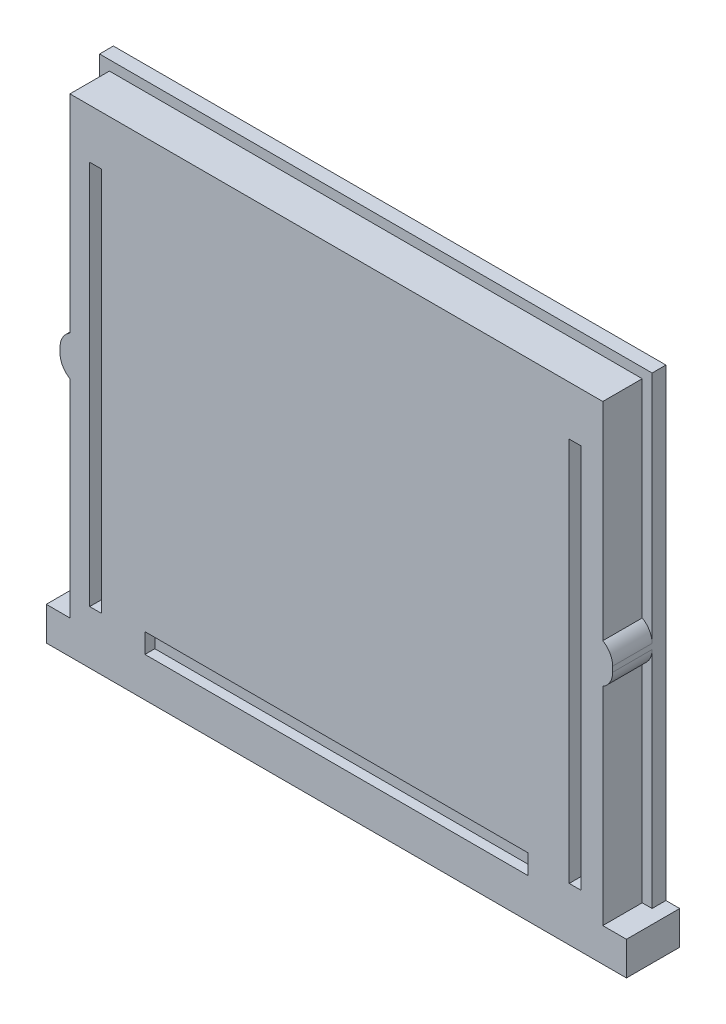
SolidWorks part; units mm, degrees
ref_plane "Спереди" through (0, 0, 0) normal (0, 0, 1) x (1, 0, 0)
ref_plane "Сверху" through (0, 0, 0) normal (0, 1, 0) x (1, 0, 0)
ref_plane "Справа" through (0, 0, 0) normal (1, 0, 0) x (0, 0, -1)
sketch "Skizze1" plane through (0, 0, 0) normal (0, 0, 1) x (1, 0, 0)
  line L1 (33.3661, 23) -> (5.3661, 23)
  line L2 (33.3661, 23) -> (33.3661, 0)
  line L3 (33.3661, 0) -> (5.3661, 0)
  line L4 (5.3661, 23) -> (5.3661, 0)
extrude "Aufsatz-Linear austragen1" add sketch "Skizze1" along normal blind 0.7
sketch "Skizze3" plane through (0, 0, 0.7) normal (0, 0, 1) x (1, 0, 0)
  line L0 (5.3661, 23) -> (5.3661, 0) construction
  line L1 (5.8661, 22.5) -> (32.8661, 22.5)
  line L2 (5.8661, 22.5) -> (5.8661, 0)
  line L3 (5.8661, 0) -> (32.8661, 0)
  line L4 (32.8661, 22.5) -> (32.8661, 0)
  line L5 (33.3661, 0) -> (33.3661, 23) construction
  line L6 (5.3661, 0) -> (33.3661, 0) construction
  line L7 (33.3661, 23) -> (5.3661, 23) construction
  dimension "D1" = 0.5
  dimension "D2" = 0.5
  dimension "D3" = 0
  dimension "D4" = 0.5
extrude "Aufsatz-Linear austragen2" add sketch "Skizze3" along normal blind 2
sketch "Skizze5" plane through (0, 0, 0) normal (0, -1, 0) x (1, 0, 0)
  line L0 (5.8661, 2.7) -> (32.8661, 2.7) construction
  line L1 (5.3661, 0) -> (33.3661, 0) construction
  line L2 (5.8661, 2.7) -> (32.8661, 2.7)
  line L3 (5.3661, 0) -> (33.3661, 0)
  line L4 (5.8661, 2.7) -> (4.6661, 2.7)
  line L5 (4.6661, 2.7) -> (4.6661, 0)
  line L6 (4.6661, 0) -> (5.3661, 0)
  line L7 (32.8661, 2.7) -> (34.0661, 2.7)
  line L8 (34.0661, 2.7) -> (34.0661, 0)
  line L9 (34.0661, 0) -> (33.3661, 0)
  dimension "D1" = 1.2
  dimension "D2" = 1.2
extrude "Aufsatz-Linear austragen4" add sketch "Skizze5" along normal blind 1.7
sketch "Skizze6" plane through (0, 0, 0) normal (0, 0, -1) x (-1, 0, 0)
  line L0 (-33.3661, 23) -> (-5.3661, 23) construction
  line L1 (-31.7661, 23) -> (-31.1661, 23)
  line L2 (-31.7661, 23) -> (-31.7661, 1)
  line L3 (-31.7661, 1) -> (-31.1661, 1)
  line L4 (-31.1661, 23) -> (-31.1661, 1)
  line L5 (-5.3661, 23) -> (-5.3661, 0) construction
  line L6 (-6.8661, 23) -> (-7.4661, 23)
  line L7 (-6.8661, 23) -> (-6.8661, 1)
  line L8 (-6.8661, 1) -> (-7.4661, 1)
  line L9 (-7.4661, 23) -> (-7.4661, 1)
  line L10 (-33.3661, 0) -> (-33.3661, 23) construction
  dimension "D1" = 1.5
  dimension "D2" = 0.6
  dimension "D3" = 0.6
  dimension "D4" = 1.6
  dimension "D5" = 22
  dimension "D6" = 22
extrude "Schnitt-Linear austragen1" cut sketch "Skizze6" against normal blind 10
sketch "Skizze7" plane through (32.8661, 0, 0) normal (1, 0, 0) x (0, 0, -1)
  line L1 (-2.7, 0) -> (-2.7, 22.5) construction
  line L2 (-2.7, 12.5) -> (-0.7, 12.5)
  line L3 (-2.7, 12.5) -> (-2.7, 10.5)
  line L4 (-2.7, 10.5) -> (-0.7, 10.5)
  line L5 (-0.7, 12.5) -> (-0.7, 10.5)
  line L6 (-0.7, 0) -> (-0.7, 22.5) construction
  line L7 (-2.7, 22.5) -> (-0.7, 22.5) construction
  dimension "D1" = 2
  dimension "D2" = 10
extrude "Aufsatz-Linear austragen5" add sketch "Skizze7" along normal blind 0.5
sketch "Skizze8" plane through (5.8661, 0, 0) normal (-1, 0, 0) x (0, 0, 1)
  line L0 (2.7, 22.5) -> (2.7, 0) construction
  line L5 (0.7, 22.5) -> (0.7, 0) construction
  line L6 (0.7, 12.5) -> (2.7, 12.5)
  line L7 (0.7, 12.5) -> (0.7, 10.5)
  line L8 (0.7, 10.5) -> (2.7, 10.5)
  line L9 (2.7, 12.5) -> (2.7, 10.5)
  dimension "D2" = 2
extrude "Aufsatz-Linear austragen6" add sketch "Skizze8" along normal blind 0.5
fillet "Verrundung1" radius 1 2 edges at (33.3661, 10.5, 1.7) (33.3661, 12.5, 1.7)
fillet "Verrundung2" radius 1 2 edges at (5.3661, 12.5, 1.7) (5.3661, 10.5, 1.7)
sketch "Skizze9" plane through (0, 0, 2.7) normal (0, 0, 1) x (1, 0, 0)
  line L1 (5.8661, 22.5) -> (5.8661, 12.5) construction
  line L2 (5.8661, 20.5) -> (32.8661, 20.5)
  line L3 (5.8661, 20.5) -> (5.8661, 23)
  line L4 (5.8661, 23) -> (32.8661, 23)
  line L5 (32.8661, 20.5) -> (32.8661, 23)
  line L6 (31.1661, 22.5) -> (7.4661, 22.5) construction
  dimension "D1" = 2
  dimension "D2" = 2.5
extrude "Aufsatz-Linear austragen7" add sketch "Skizze9" against normal blind 2.7
sketch "Skizze10" plane through (0, 23, 0) normal (0, 1, 0) x (1, 0, 0)
  line L1 (5.3661, 0) -> (33.3661, 0)
  line L2 (5.3661, 0) -> (5.3661, -0.7)
  line L3 (5.3661, -0.7) -> (33.3661, -0.7)
  line L4 (33.3661, 0) -> (33.3661, -0.7)
extrude "Aufsatz-Linear austragen8" add sketch "Skizze10" along normal blind 0.5
sketch "Skizze11" plane through (0, 0, 2.7) normal (0, 0, 1) x (1, 0, 0)
  line L0 (34.0661, -1.7) -> (34.0661, 0) construction
  line L1 (9.6661, 1.3) -> (29.0661, 1.3)
  line L2 (9.6661, 1.3) -> (9.6661, 0.3)
  line L3 (9.6661, 0.3) -> (29.0661, 0.3)
  line L4 (29.0661, 1.3) -> (29.0661, 0.3)
  line L5 (4.6661, -1.7) -> (4.6661, 0) construction
  line L6 (34.0661, -1.7) -> (4.6661, -1.7) construction
  dimension "D1" = 1
  dimension "D2" = 5
  dimension "D3" = 5
  dimension "D4" = 2
extrude "Schnitt-Linear austragen2" cut sketch "Skizze11" against normal blind 0.5
